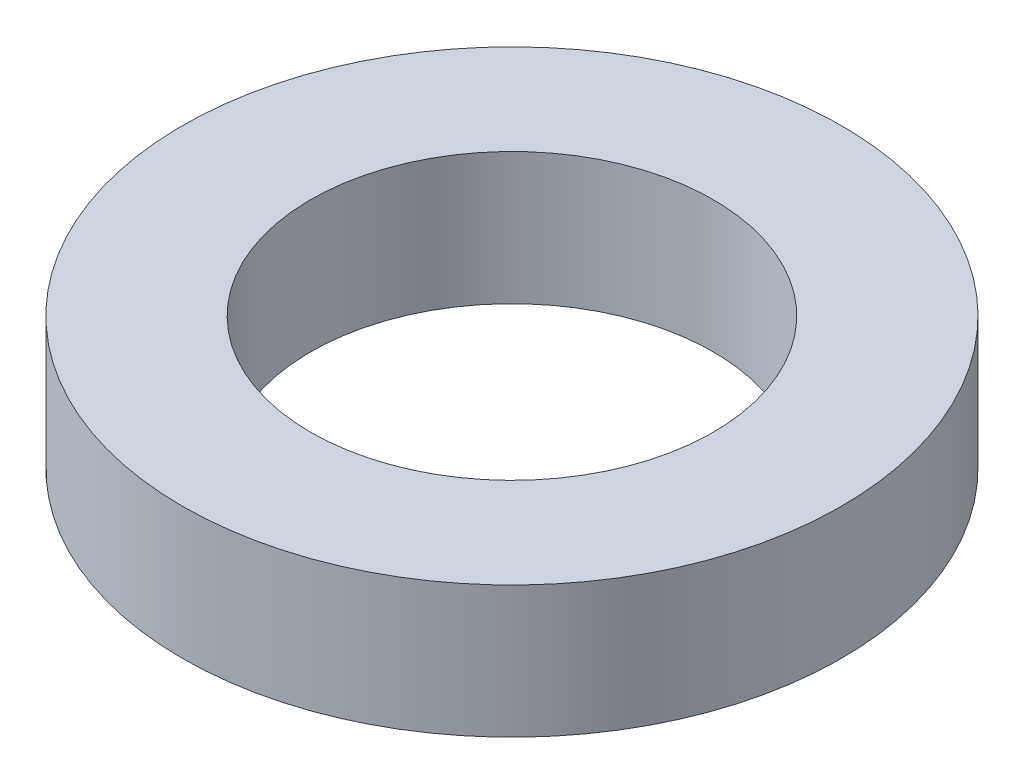
SolidWorks part; units mm, degrees
ref_plane "Front Plane" through (0, 0, 0) normal (0, 0, 1) x (1, 0, 0)
ref_plane "Top Plane" through (0, 0, 0) normal (0, 1, 0) x (1, 0, 0)
ref_plane "Right Plane" through (0, 0, 0) normal (1, 0, 0) x (0, 0, -1)
sketch "Sketch1" plane through (0, 0, 0) normal (0, 1, 0) x (1, 0, 0)
  circle A0 centre (0, 0) radius 45
  dimension "FLANGE_OD" = 90
extrude "Boss-Extrude1" add sketch "Sketch1" along normal blind 18
sketch "Sketch2" plane through (0, 0, 0) normal (0, 1, 0) x (1, 0, 0)
  circle A0 centre (0, 0) radius 27.5
  dimension "BORE_D" = 55
extrude "Cut-Extrude1" cut sketch "Sketch2" along normal through all
sketch "Sketch3" plane through (0, 18, 0) normal (0, 1, 0) x (1, 0, 0)
  circle A0 centre (0, 0) radius 19.7763 construction
  circle A1 centre (-19.7763, 0) radius 2.3067
  dimension "BOLT_D" = 4.6133
  dimension "BOLT_PCD" = 39.5526
extrude "Cut-Extrude2" cut sketch "Sketch3" against normal blind 15.8808 rebuild error yes
pattern_circular "CirPattern1" count 8 over 360 rebuild error yes
